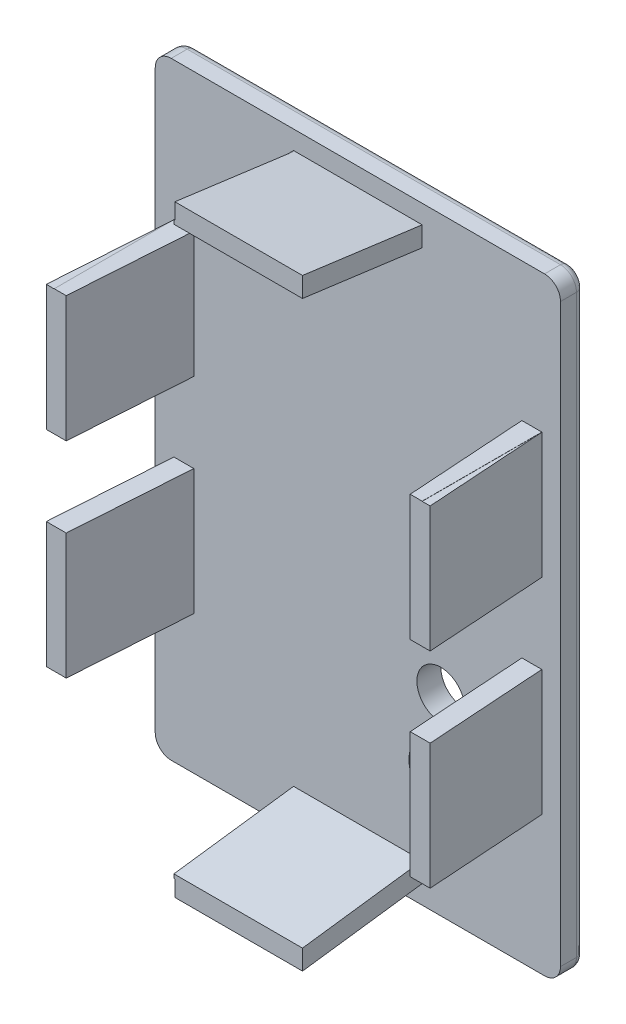
SolidWorks part; units mm, degrees
material "PLA"
ref_plane "Alzado" through (0, 0, 0) normal (0, 0, 1) x (1, 0, 0)
ref_plane "Planta" through (0, 0, 0) normal (0, 1, 0) x (1, 0, 0)
ref_plane "Vista lateral" through (0, 0, 0) normal (1, 0, 0) x (0, 0, -1)
sketch "Croquis1" plane through (0, 0, 0) normal (0, 0, 1) x (1, 0, 0)
  line L1 (25.4, 38.1) -> (-25.4, 38.1)
  line L2 (25.4, 38.1) -> (25.4, -38.1)
  line L3 (25.4, -38.1) -> (-25.4, -38.1)
  line L4 (-25.4, 38.1) -> (-25.4, -38.1)
  line L5 (25.4, 38.1) -> (-25.4, -38.1) construction
  line L6 (25.4, -38.1) -> (-25.4, 38.1) construction
  point P0 (0, 0)
  dimension "D1" = 76.2
  dimension "D2" = 50.8
extrude "Saliente-Extruir1" add sketch "Croquis1" along normal blind 18
sketch "Croquis2" plane through (0, 0, 18) normal (0, 0, 1) x (1, 0, 0)
  line L0 (25.4, 38.1) -> (-25.4, 38.1) construction
  line L1 (-23.06, 35.76) -> (23.06, 35.76)
  line L2 (-23.06, 35.76) -> (-23.06, -35.76)
  line L3 (-23.06, -35.76) -> (23.06, -35.76)
  line L4 (23.06, 35.76) -> (23.06, -35.76)
  line L5 (-25.4, -38.1) -> (25.4, -38.1) construction
  line L6 (-25.4, 38.1) -> (-25.4, -38.1) construction
  line L7 (25.4, -38.1) -> (25.4, 38.1) construction
  line L9 (-25.4, 38.1) -> (25.4, 38.1)
  line L10 (-25.4, 38.1) -> (-25.4, -38.1)
  line L11 (-25.4, -38.1) -> (25.4, -38.1)
  line L12 (25.4, 38.1) -> (25.4, -38.1)
  line L13 (-19.4, 32.1) -> (19.4, 32.1)
  line L14 (-19.4, 32.1) -> (-19.4, -32.1)
  line L15 (-19.4, -32.1) -> (19.4, -32.1)
  line L16 (19.4, 32.1) -> (19.4, -32.1)
  line M9 (-25.4, 38.1) -> (-25.4, -38.1)
  line M10 (-25.4, -38.1) -> (25.4, -38.1)
  line M11 (25.4, -38.1) -> (25.4, 38.1)
  line M12 (25.4, 38.1) -> (-25.4, 38.1)
  dimension "D1" = 2.34
  dimension "D2" = 2.34
  dimension "D3" = 2.34
  dimension "D4" = 2.34
  dimension "D5" = 6
  dimension "D6" = 6
  dimension "D7" = 6
  dimension "D8" = 6
extrude "Cortar-Extruir1" cut sketch "Croquis2" against normal blind 15 contours L1 L4 L3 L2 M12 M9 M10 M11 | L16 L13 L14 L15 region at (0, 37.1842, 18) region at (0, 0, 18)
sketch "Croquis3" plane through (0, 0, 18) normal (0, 0, 1) x (1, 0, 0)
  line L0 (-23.06, 35.76) -> (-23.06, -35.76) construction
  line L1 (-23.06, 22.1) -> (-19.4, 22.1)
  line L2 (-23.06, 22.1) -> (-23.06, -22.1)
  line L3 (-23.06, -22.1) -> (-19.4, -22.1)
  line L4 (-19.4, 22.1) -> (-19.4, -22.1)
  line L5 (-19.4, 32.1) -> (-19.4, -32.1) construction
  line L6 (-19.4, -32.1) -> (19.4, -32.1) construction
  line L7 (-9.4, -32.1) -> (9.3837, -32.1)
  line L8 (-9.4, -32.1) -> (-9.4, -35.76)
  line L9 (-9.4, -35.76) -> (9.3837, -35.76)
  line L10 (9.3837, -32.1) -> (9.3837, -35.76)
  line L11 (-23.06, -35.76) -> (23.06, -35.76) construction
  line L12 (19.4, 32.1) -> (19.4, -32.1) construction
  line L13 (19.4, -22.1) -> (23.06, -22.1)
  line L14 (19.4, -22.1) -> (19.4, 22.1)
  line L15 (19.4, 22.1) -> (23.06, 22.1)
  line L16 (23.06, -22.1) -> (23.06, 22.1)
  line L17 (23.06, 35.76) -> (23.06, -35.76) construction
  line L18 (-23.06, 35.76) -> (23.06, 35.76) construction
  line L19 (-9.4, 35.76) -> (9.4, 35.76)
  line L20 (-9.4, 35.76) -> (-9.4, 32.1)
  line L21 (-9.4, 32.1) -> (9.4, 32.1)
  line L22 (9.4, 35.76) -> (9.4, 32.1)
  line L23 (-19.4, 32.1) -> (19.4, 32.1) construction
  line L24 (-19.4, 32.1) -> (-19.4, -32.1) construction
  line L25 (19.4, 32.1) -> (19.4, -32.1) construction
  dimension "D1" = 10
  dimension "D2" = 10
  dimension "D3" = 10
  dimension "D4" = 10
  dimension "D5" = 10
  dimension "D6" = 10
  dimension "D7" = 10
extrude "Cortar-Extruir2" [suppressed] cut sketch "Croquis3" against normal blind 7
fillet "Redondeo1" [suppressed] radius 2
fillet "Redondeo2" [suppressed] radius 1
sketch "Croquis5" [suppressed] plane through (0, -38.1, 0) normal (0, -1, 0) x (1, 0, 0)
  line L0 (-23.4, 3) -> (23.4, 3) construction
  line L1 (-3, 3) -> (3, 3)
  line L2 (-3, 3) -> (-3, 1.5)
  line L3 (-3, 1.5) -> (3, 1.5)
  line L4 (3, 3) -> (3, 1.5)
  line L5 (0, 1) -> (0, 3) construction
  line L6 (-23.4, 1) -> (23.4, 1) construction
  dimension "D1" = 3
  dimension "D2" = 3
  dimension "D3" = 1.5
extrude "Cortar-Extruir4" [suppressed] cut sketch "Croquis5" against normal blind 6
sketch "Croquis6" plane through (0, 0, 18) normal (0, 0, 1) x (1, 0, 0)
  line L0 (-23.06, 35.76) -> (-8.06, 35.76)
  line L1 (-23.06, 35.76) -> (23.06, 35.76) construction
  line L2 (-8.06, 35.76) -> (-8.06, 32.1)
  line L3 (-19.4, 32.1) -> (19.4, 32.1) construction
  line L4 (-8.06, 32.1) -> (-19.4, 32.1)
  line L5 (-19.4, 32.1) -> (-19.4, 20.76)
  line L6 (-19.4, 32.1) -> (-19.4, -32.1) construction
  line L7 (-19.4, 20.76) -> (-23.06, 20.76)
  line L8 (-23.06, 35.76) -> (-23.06, -35.76) construction
  line L9 (-23.06, 20.76) -> (-23.06, 35.76)
  line L10 (23.06, 35.76) -> (8.06, 35.76)
  line L11 (-23.06, 35.76) -> (23.06, 35.76) construction
  line L12 (8.06, 35.76) -> (8.06, 32.1)
  line L13 (8.06, 32.1) -> (19.4, 32.1)
  line L14 (19.4, 32.1) -> (19.4, -32.1) construction
  line L15 (19.4, 32.1) -> (19.4, -32.1) construction
  line L16 (19.4, 32.1) -> (19.4, 20.76)
  line L17 (19.4, 20.76) -> (23.06, 20.76)
  line L18 (23.06, 35.76) -> (23.06, -35.76) construction
  line L19 (23.06, 20.76) -> (23.06, 35.76)
  line L20 (-23.06, -35.76) -> (-23.06, -20.76)
  line L21 (-23.06, 35.76) -> (-23.06, -35.76) construction
  line L22 (-23.06, -20.76) -> (-19.4, -20.76)
  line L23 (-19.4, 32.1) -> (-19.4, -32.1) construction
  line L24 (-19.4, -20.76) -> (-19.4, -32.1)
  line L25 (-19.4, -32.1) -> (-8.06, -32.1)
  line L26 (-19.4, -32.1) -> (19.4, -32.1) construction
  line L27 (-8.06, -32.1) -> (-8.06, -35.76)
  line L28 (-23.06, -35.76) -> (23.06, -35.76) construction
  line L29 (-8.06, -35.76) -> (-23.06, -35.76)
  line L30 (23.06, -35.76) -> (8.06, -35.76)
  line L31 (-23.06, -35.76) -> (23.06, -35.76) construction
  line L32 (8.06, -35.76) -> (8.06, -32.1)
  line L33 (-19.4, -32.1) -> (19.4, -32.1) construction
  line L34 (8.06, -32.1) -> (19.4, -32.1)
  line L35 (19.4, -32.1) -> (19.4, -20.76)
  line L36 (19.4, -20.76) -> (23.06, -20.76)
  line L37 (23.06, 35.76) -> (23.06, -35.76) construction
  line L38 (23.06, -20.76) -> (23.06, -35.76)
  dimension "D1" = 15
  dimension "D2" = 15
  dimension "D3" = 15
  dimension "D4" = 15
  dimension "D5" = 15
  dimension "D6" = 15
  dimension "D7" = 15
  dimension "D8" = 15
extrude "Cortar-Extruir8" cut sketch "Croquis6" against normal blind 15
sketch "Croquis10" plane through (0, -20.76, 0) normal (0, -1, 0) x (-1, 0, 0)
  line L0 (23.06, -18) -> (24.06, -18)
  line L1 (24.06, -18) -> (23.06, -3)
  line L2 (23.06, -3) -> (23.06, -18)
  line L3 (-23.06, -18) -> (-24.06, -18)
  line L4 (-24.06, -18) -> (-23.06, -3)
  line L5 (-23.06, -3) -> (-23.06, -18)
  dimension "D1" = 1
  dimension "D2" = 1
extrude "Saliente-Extruir3" add sketch "Croquis10" against normal blind 41.5
sketch "Croquis11" plane through (0, -20.76, 0) normal (0, -1, 0) x (1, 0, 0)
  line L0 (-19.4, 18) -> (-21.56, 18)
  line L1 (-19.4, 18) -> (-24.06, 18) construction
  line L2 (-21.56, 18) -> (-20.56, 3)
  line L3 (-19.4, 3) -> (-23.06, 3) construction
  line L4 (-20.56, 3) -> (-19.4, 3)
  line L5 (-19.4, 18) -> (-19.4, 3)
  dimension "D1" = 2.5
  dimension "D2" = 1.16
extrude "Cortar-Extruir9" cut sketch "Croquis11" against normal blind 51.5
sketch "Croquis12" plane through (0, -20.76, 0) normal (0, -1, 0) x (1, 0, 0)
  line L0 (19.4, 18) -> (19.4, 3)
  line L1 (19.4, 3) -> (20.56, 3)
  line L2 (23.06, 3) -> (19.4, 3) construction
  line L3 (20.56, 3) -> (21.56, 18)
  line L4 (24.06, 18) -> (19.4, 18) construction
  line L5 (21.56, 18) -> (19.4, 18)
  dimension "D1" = 2.5
  dimension "D2" = 1.16
extrude "Cortar-Extruir10" cut sketch "Croquis12" against normal blind 51.5
sketch "Croquis13" plane through (8.06, 0, 0) normal (1, 0, 0) x (0, 0, -1)
  line L0 (-18, -35.76) -> (-18, -37.76)
  line L1 (-18, -37.76) -> (-3, -35.76)
  line L2 (-3, -35.76) -> (-18, -35.76)
  line L3 (-18, 35.76) -> (-18, 37.76)
  line L4 (-18, 37.76) -> (-3, 35.76)
  line L5 (-3, 35.76) -> (-18, 35.76)
  dimension "D1" = 2
  dimension "D2" = 2
extrude "Saliente-Extruir4" add sketch "Croquis13" against normal blind 16
sketch "Croquis14" plane through (8.06, 0, 0) normal (1, 0, 0) x (0, 0, -1)
  line L0 (-3, -32.1) -> (-18, -32.1)
  line L1 (-18, -32.1) -> (-18, -35.26)
  line L2 (-18, -32.1) -> (-18, -37.76) construction
  line L3 (-18, -35.26) -> (-3, -33.26)
  line L4 (-3, -32.1) -> (-3, -35.76) construction
  line L5 (-3, -33.26) -> (-3, -32.1)
  line L6 (-18, 32.1) -> (-18, 35.26)
  line L7 (-18, 37.76) -> (-18, 32.1) construction
  line L8 (-18, 35.26) -> (-3, 33.26)
  line L9 (-3, 35.76) -> (-3, 32.1) construction
  line L10 (-3, 33.26) -> (-3, 32.1)
  line L11 (-3, 32.1) -> (-18, 32.1)
  dimension "D1" = 2.5
  dimension "D2" = 1.16
  dimension "D3" = 2.5
  dimension "D4" = 1.16
extrude "Cortar-Extruir11" cut sketch "Croquis14" against normal blind 16.5
fillet "Redondeo3" radius 2 4 edges at (25.4, 38.1, 1.5) (-25.4, 38.1, 1.5) (-25.4, -38.1, 1.5) (25.4, -38.1, 1.5)
fillet "Redondeo4" radius 1 8 edges at (-24.8142, 37.5142, 0) (-25.4, 0, 0) (-24.8142, -37.5142, 0) (0, -38.1, 0) (24.8142, -37.5142, 0) (25.4, 0, 0) (24.8142, 37.5142, 0) (0, 38.1, 0)
sketch "Croquis15" plane through (0, 0, 18) normal (0, 0, 1) x (1, 0, 0)
  line L0 (-24.06, -0.01) -> (24.06, -0.01) construction
  line L1 (-24.06, 20.74) -> (-24.06, -20.76) construction
  line L2 (24.06, 20.74) -> (24.06, -20.76) construction
  line L4 (-24.06, 4.99) -> (24.06, 4.99)
  line L5 (-24.06, 4.99) -> (-24.06, -5.01)
  line L6 (-24.06, -5.01) -> (24.06, -5.01)
  line L7 (24.06, 4.99) -> (24.06, -5.01)
  dimension "D1" = 5
  dimension "D2" = 5
extrude "Cortar-Extruir12" cut sketch "Croquis15" against normal blind 15
sketch "Croquis16" plane through (0, -38.1, 0) normal (0, -1, 0) x (1, 0, 0)
  line L0 (-23.4, 3) -> (23.4, 3) construction
  line L1 (-4, 3) -> (4, 3)
  line L2 (-4, 3) -> (-4, 1.5)
  line L3 (-4, 1.5) -> (4, 1.5)
  line L4 (4, 3) -> (4, 1.5)
  dimension "D1" = 1.5
  dimension "D2" = 8
  dimension "D3" = 4
extrude "Cortar-Extruir13" cut sketch "Croquis16" against normal blind 2
sketch "Croquis17" plane through (0, 0, 3) normal (0, 0, 1) x (1, 0, 0)
  line L1 (-23.4, -38.1) -> (-4, -38.1) construction
  line L2 (25.4, -36.1) -> (25.4, 36.1) construction
  circle A0 centre (10.4, -23.1) radius 4
  circle A1 centre (10.4, -14.1) radius 3
  dimension "D3" = 8
  dimension "D4" = 6
  dimension "D1" = 15
  dimension "D2" = 15
  dimension "D7" = 9
  dimension "D8" = 15
extrude "Cortar-Extruir14" cut sketch "Croquis17" against normal blind 10
